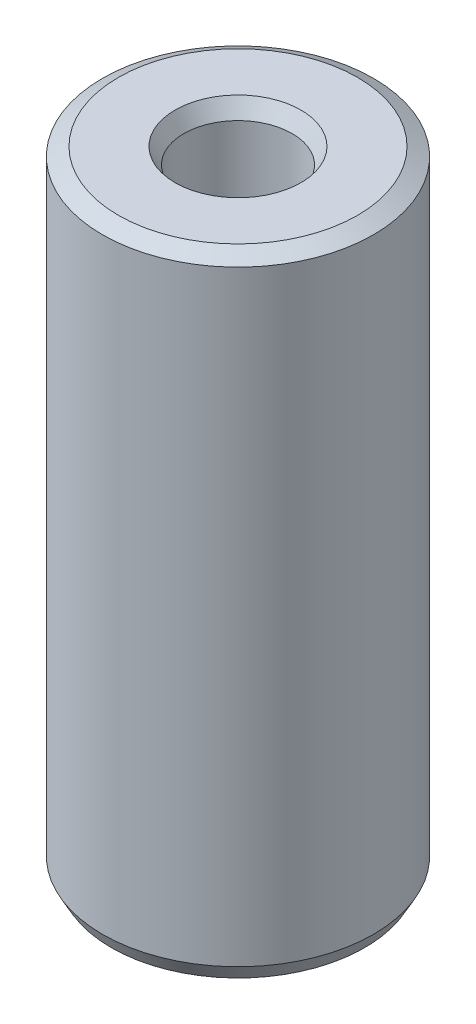
SolidWorks part; units mm, degrees
ref_plane "Front Plane" through (0, 0, 0) normal (0, 0, 1) x (1, 0, 0)
ref_plane "Top Plane" through (0, 0, 0) normal (0, 1, 0) x (1, 0, 0)
ref_plane "Right Plane" through (0, 0, 0) normal (1, 0, 0) x (0, 0, -1)
sketch "Sketch1" plane through (0, 0, 0) normal (0, 1, 0) x (1, 0, 0)
  circle A0 centre (0, 0) radius 20
  dimension "SLEEVE_OD" = 40
extrude "Boss-Extrude1" add sketch "Sketch1" along normal blind 93.0772
sketch "Sketch2" plane through (0, 0, 0) normal (0, 1, 0) x (1, 0, 0)
  circle A0 centre (0, 0) radius 7.9913
  dimension "BORE_D" = 15.9826
extrude "Cut-Extrude1" cut sketch "Sketch2" along normal through all
chamfer "Chamfer1" distance 1.2992 angle 61.144 4 edges at (0, 93.0772, 7.9913) (0, 0, 7.9913) (0, 0, 20) (0, 93.0772, 20) first distance on face at (0, 93.0772, 7.9913) first distance on face at (0, 0, 7.9913) first distance on face at (0, 93.0772, 20)
